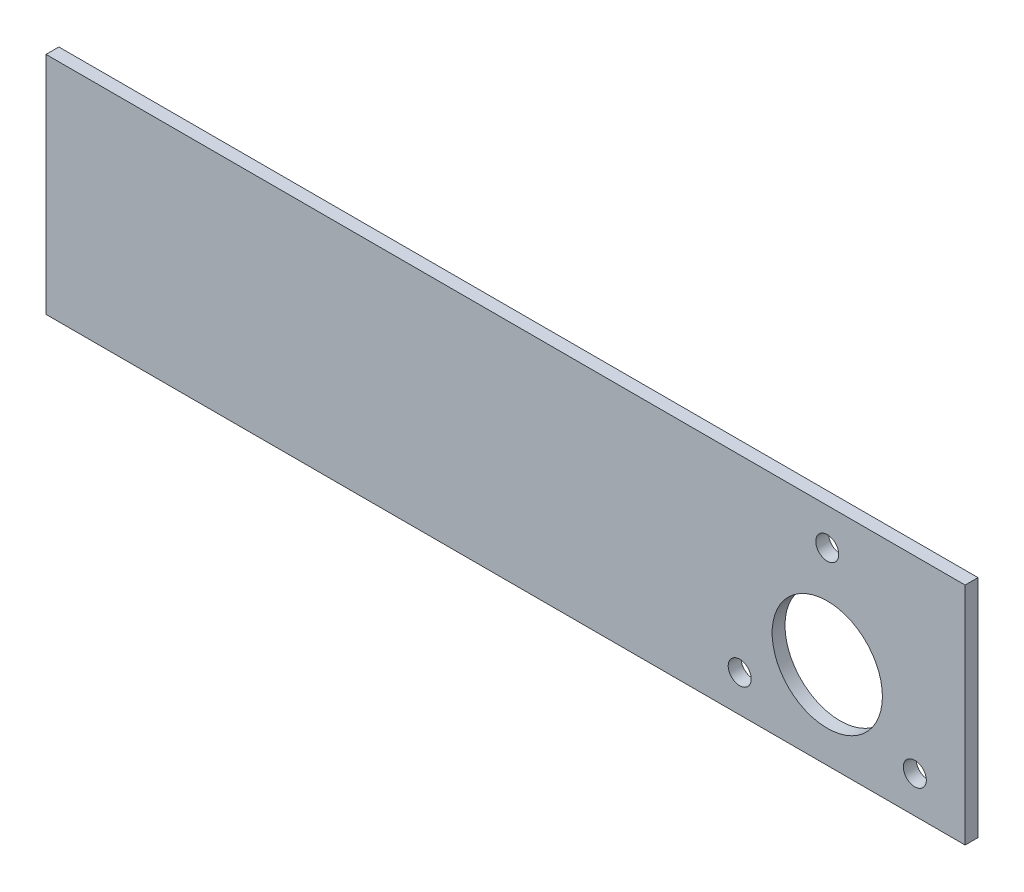
SolidWorks part; units mm, degrees
ref_plane "Front Plane" through (0, 0, 0) normal (0, 0, 1) x (1, 0, 0)
ref_plane "Top Plane" through (0, 0, 0) normal (0, 1, 0) x (1, 0, 0)
ref_plane "Right Plane" through (0, 0, 0) normal (1, 0, 0) x (0, 0, -1)
sketch "Sketch1" plane through (0, 0, 0) normal (0, 0, 1) x (1, 0, 0)
  line L0 (0, 0) -> (0, 11) construction
  line L1 (0, 0) -> (-9.5263, -5.5) construction
  line L2 (9.5263, -5.5) -> (0, 0) construction
  circle A0 centre (0, 11) radius 1.25
  circle A2 centre (-9.5263, -5.5) radius 1.25
  circle A3 centre (9.5263, -5.5) radius 1.25
  circle A4 centre (0, 0) radius 6
  dimension "D1" = 12
  dimension "D2" = 2.5
  dimension "D3" = 11
sketch "Sketch2" plane through (0, 0, 0) normal (0, 0, 1) x (1, 0, 0)
  line L1 (-85, -9.5) -> (15, -9.5)
  line L2 (-85, -9.5) -> (-85, 15)
  line L3 (-85, 15) -> (15, 15)
  line L4 (15, -9.5) -> (15, 15)
  dimension "D1" = 4
  dimension "D2" = 4
  dimension "D3" = 100
  dimension "D4" = 15
base flange "Base-Flange1" sketch "Sketch2" thickness 1.4 reverse thickness direction no parameters "D1"=3
extrude "Cut-Extrude1" cut sketch "Sketch1" against normal blind 10 normal cut yes
sketch "Bend-Lines1" [suppressed] plane through (0, 0, 0) normal (0, 1, 0) x (1, 0, 0)
sketch "Bounding-Box1" [suppressed] plane through (0, 0, 0) normal (0, 1, 0) x (1, 0, 0)
sheet metal parameters "Sheet-Metal1" thickness 1.4 parameters "D1"=3
flat pattern "Flat-Pattern1" [suppressed]
sketch "Bend-Lines2" plane through (0, 0, 0) normal (0, 1, 0) x (1, 0, 0)
sketch3d "Bounding-Box2" [suppressed]
  line L0 (25, -9.5, 0) -> (-15, -9.5, 0) construction
  line L1 (25, 15, 0) -> (-15, 15, 0) construction
  line L2 (25, -9.5, 0) -> (25, 15, 0) construction
  line L3 (-15, -9.5, 0) -> (-15, 15, 0) construction
sheet metal parameters "Sheet-Metal2" thickness 1.4 parameters "D1"=3
flat pattern "Flat-Pattern1"
sketch "Bend-Lines2" plane through (0, 0, 0) normal (0, 1, 0) x (1, 0, 0)
sketch3d "Bounding-Box2" [suppressed]
  line L0 (-85, -9.5, 0) -> (15, -9.5, 0) construction
  line L1 (-85, 15, 0) -> (15, 15, 0) construction
  line L2 (-85, -9.5, 0) -> (-85, 15, 0) construction
  line L3 (15, -9.5, 0) -> (15, 15, 0) construction
